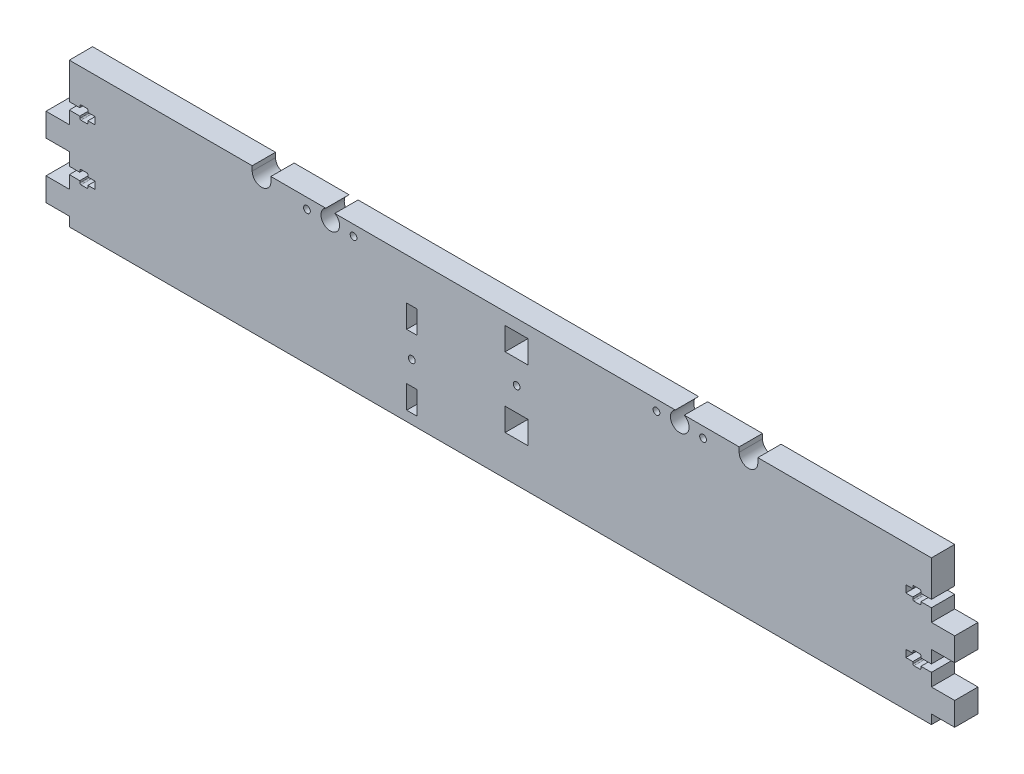
SolidWorks part; units mm, degrees
ref_plane "Front Plane" through (0, 0, 0) normal (0, 0, 1) x (1, 0, 0)
ref_plane "Top Plane" through (0, 0, 0) normal (0, 1, 0) x (1, 0, 0)
ref_plane "Right Plane" through (0, 0, 0) normal (1, 0, 0) x (0, 0, -1)
sketch "Sketch1" plane through (0, 0, 0) normal (0, 0, 1) x (1, 0, 0)
  line L0 (0, 0) -> (-185, 0)
  line L1 (-185, 0) -> (-185, -62) construction
  line L2 (0, -62) -> (-185, -62)
  line L3 (-185, -62) -> (-185, -58)
  line L4 (-185, -58) -> (-195, -58)
  line L5 (-195, -58) -> (-195, -48)
  line L6 (-195, -48) -> (-185, -48)
  line L7 (-185, -48) -> (-185, -34)
  line L8 (-185, -34) -> (-195, -34)
  line L9 (-195, -34) -> (-195, -24)
  line L10 (-195, -24) -> (-185, -24)
  line L11 (0, -62) -> (0, 0)
  line L12 (-185, -24) -> (-185, 0)
  line L13 (-195, -58) -> (-195, -24) construction
  line L14 (-195, -29) -> (-185, -29) construction
  line L15 (-195, -53) -> (-185, -53) construction
  dimension "D1" = 185
  dimension "D2" = 10
  dimension "D3" = 10
  dimension "D4" = 10
  dimension "D5" = 24
  dimension "D6" = 29
  dimension "D7" = 62
extrude "MainBody" add sketch "Sketch1" along normal blind 10
sketch "Sketch3" plane through (0, 0, 10) normal (0, 0, 1) x (1, 0, 0)
  line L0 (-185, -17) -> (-174, -17) construction
  line L1 (-185, 0) -> (-185, -24) construction
  line L2 (-185, -18.55) -> (-180.5, -18.55)
  line L3 (-180.5, -18.55) -> (-180.5, -19.35)
  line L4 (-180, -19.85) -> (-177.5, -19.85)
  line L5 (-177, -19.35) -> (-177, -18.55)
  line L6 (-177, -18.55) -> (-174, -18.55)
  line L7 (-174, -18.55) -> (-174, -15.45)
  line L8 (-180.5, -18.55) -> (-177, -18.55) construction
  line L9 (-195, -24) -> (-195, -34) construction
  line L10 (-180.5, -15.45) -> (-177, -15.45) construction
  line L11 (-177, -15.45) -> (-174, -15.45)
  line L12 (-177, -14.65) -> (-177, -15.45)
  line L13 (-180, -14.15) -> (-177.5, -14.15)
  line L14 (-180.5, -15.45) -> (-180.5, -14.65)
  line L15 (-185, -15.45) -> (-180.5, -15.45)
  line L16 (-185, -18.55) -> (-185, -15.45)
  line L17 (-185, -24) -> (-185, -34) construction
  line L19 (-195, -24) -> (-195, -34) construction
  line L20 (-195, -29) -> (-185, -29) construction
  line L21 (-180.5, -42.55) -> (-177, -42.55) construction
  line L22 (-180.5, -39.45) -> (-177, -39.45) construction
  line L23 (-185, -41) -> (-174, -41) construction
  line L24 (-185, -39.45) -> (-185, -42.55)
  line L25 (-185, -42.55) -> (-180.5, -42.55)
  line L26 (-180.5, -42.55) -> (-180.5, -43.35)
  line L27 (-180, -43.85) -> (-177.5, -43.85)
  line L28 (-177, -43.35) -> (-177, -42.55)
  line L29 (-177, -42.55) -> (-174, -42.55)
  line L30 (-174, -39.45) -> (-174, -42.55)
  line L31 (-177, -39.45) -> (-174, -39.45)
  line L32 (-177, -38.65) -> (-177, -39.45)
  line L33 (-180, -38.15) -> (-177.5, -38.15)
  line L34 (-180.5, -39.45) -> (-180.5, -38.65)
  line L35 (-185, -39.45) -> (-180.5, -39.45)
  line L36 (-180.5, -15.45) -> (-177, -15.45) construction
  arc A0 (-177.5, -19.85) -> (-177, -19.35) centre (-177.5, -19.35) ccw
  arc A1 (-180.5, -19.35) -> (-180, -19.85) centre (-180, -19.35) ccw
  arc A2 (-180.5, -14.65) -> (-180, -14.15) centre (-180, -14.65) cw
  arc A3 (-177.5, -14.15) -> (-177, -14.65) centre (-177.5, -14.65) cw
  arc A4 (-177.5, -43.85) -> (-177, -43.35) centre (-177.5, -43.35) ccw
  arc A5 (-180.5, -43.35) -> (-180, -43.85) centre (-180, -43.35) ccw
  arc A6 (-180.5, -38.65) -> (-180, -38.15) centre (-180, -38.65) cw
  arc A7 (-177.5, -38.15) -> (-177, -38.65) centre (-177.5, -38.65) cw
  point P6 (-195, -29)
  point P15 (-177, -19.85)
  point P18 (-180.5, -19.85)
  point P29 (-180.5, -14.15)
  point P30 (-177, -14.15)
  point P62 (-177, -43.85)
  point P63 (-180.5, -43.85)
  point P64 (-180.5, -38.15)
  point P65 (-177, -38.15)
  dimension "D2" = 8
  dimension "D7" = 0.5
  dimension "D1" = 11
  dimension "D3" = 1.55
  dimension "D4" = 2.85
  dimension "D5" = 12
  dimension "D6" = 3.5
extrude "ScrewCutouts" cut sketch "Sketch3" against normal through all
mirror "Mirror1" about plane through (0, 0, 0) normal (1, 0, 0) of "ScrewCutouts", "MainBody"
sketch "Sketch2" plane through (0, 0, 10) normal (0, 0, 1) x (1, 0, 0)
  line L0 (0, 0) -> (0, -62) construction
  line L1 (-185, -62) -> (185, -62) construction
  line L2 (2, 0) -> (2, -62) construction
  line L3 (185, 0) -> (-185, 0) construction
  line L4 (-63, -4.5) -> (-83, -4.5) construction
  line L5 (-73, -7.5) -> (-73, 0.5) construction
  line L6 (77, -7.5) -> (77, 0.5) construction
  line L7 (67, -4.5) -> (87, -4.5) construction
  circle A0 centre (-73, -3.5) radius 4
  circle A1 centre (-83, -4.5) radius 1.45
  circle A2 centre (-63, -4.5) radius 1.45
  circle A3 centre (67, -4.5) radius 1.45
  circle A4 centre (87, -4.5) radius 1.45
  circle A5 centre (77, -3.5) radius 4
  dimension "D1" = 2.9
  dimension "D2" = 8
  dimension "D4" = 3.5
  dimension "D5" = 75
  dimension "D6" = 2
  dimension "D3" = 10
  dimension "D7" = 1
extrude "RodCutouts" cut sketch "Sketch2" against normal through all
sketch "Sketch4" plane through (0, 0, 10) normal (0, 0, 1) x (1, 0, 0)
  line L0 (77, -3.5) -> (-73, -3.5) construction
  line L1 (2, -3.5) -> (2, -62) construction
  line L2 (-185, -62) -> (185, -62) construction
  line L3 (7, -44.9) -> (7, -5.1) construction
  line L4 (75.0635, 0) -> (-71.0635, 0) construction
  line L5 (7, -10) -> (7, -40) construction
  line L6 (2.05, -5.1) -> (11.95, -5.1)
  line L7 (2.05, -5.1) -> (2.05, -14.9)
  line L8 (2.05, -14.9) -> (11.95, -14.9)
  line L9 (11.95, -5.1) -> (11.95, -14.9)
  line L10 (2.05, -5.1) -> (11.95, -14.9) construction
  line L11 (2.05, -14.9) -> (11.95, -5.1) construction
  line L12 (2.05, -35.1) -> (11.95, -35.1)
  line L13 (2.05, -35.1) -> (2.05, -44.9)
  line L14 (2.05, -44.9) -> (11.95, -44.9)
  line L15 (11.95, -35.1) -> (11.95, -44.9)
  line L16 (2.05, -35.1) -> (11.95, -44.9) construction
  line L17 (2.05, -44.9) -> (11.95, -35.1) construction
  circle A0 centre (7, -25) radius 1.45
  point P12 (7, -10)
  point P17 (7, -40)
  dimension "D8" = 2.9
  dimension "D1" = 9.9
  dimension "D2" = 9.8
  dimension "D3" = 9.9
  dimension "D4" = 9.8
  dimension "D5" = 30
  dimension "D6" = 10
  dimension "D7" = 5
extrude "Cut-Extrude3" cut sketch "Sketch4" against normal through all
sketch "Sketch5" plane through (0, 0, 10) normal (0, 0, 1) x (1, 0, 0)
  line L0 (-38, 0) -> (-38, -62) construction
  line L1 (-74.9365, 0) -> (-185, 0) construction
  line L2 (-185, -62) -> (185, -62) construction
  line L3 (-40.2, -27.675) -> (-40.2, -47.825) construction
  line L4 (-40.2, -17.875) -> (-35.8, -17.875)
  line L5 (-40.2, -17.875) -> (-40.2, -27.675)
  line L6 (-40.2, -27.675) -> (-35.8, -27.675)
  line L7 (-35.8, -17.875) -> (-35.8, -27.675)
  line L8 (-40.2, -17.875) -> (-35.8, -27.675) construction
  line L9 (-40.2, -27.675) -> (-35.8, -17.875) construction
  line L10 (-40.2, -47.825) -> (-35.8, -47.825)
  line L11 (-40.2, -47.825) -> (-40.2, -57.725)
  line L12 (-40.2, -57.725) -> (-35.8, -57.725)
  line L13 (-35.8, -47.825) -> (-35.8, -57.725)
  line L14 (-40.2, -47.825) -> (-35.8, -57.725) construction
  line L15 (-40.2, -57.725) -> (-35.8, -47.825) construction
  line L16 (-35.8, -47.825) -> (-35.8, -27.675) construction
  line L17 (-40.2, -37.75) -> (-35.8, -37.75) construction
  line L18 (-73, -3.5) -> (77, -3.5) construction
  line L19 (2, -3.5) -> (2, -62) construction
  line L20 (2, -32.75) -> (-195, -32.75) construction
  line L21 (-195, -24) -> (-195, -34) construction
  line L22 (-31.6, 8.9944) -> (-31.6, 5) construction
  line L23 (75.0635, 0) -> (-71.0635, 0) construction
  line L24 (-28.4, 8.9944) -> (-28.4, 5)
  line L25 (-34.8, 8.9944) -> (-34.8, 5)
  circle A0 centre (-38, -37.75) radius 1.45
  arc A1 (-28.4, 8.9944) -> (-34.8, 8.9944) centre (-31.6, 8.9944) ccw
  arc A2 (-34.8, 5) -> (-28.4, 5) centre (-31.6, 5) ccw
  point P6 (-38, -22.775)
  point P11 (-38, -52.775)
  point P34 (-31.6, 6.9972)
  dimension "D3" = 9.9
  dimension "D4" = 9.8
  dimension "D5" = 30
  dimension "D6" = 2.9
  dimension "D9" = 3.2
  dimension "D1" = 4.4
  dimension "D2" = 0
  dimension "D7" = 40
  dimension "D8" = 5
  dimension "D10" = 5
  dimension "D11" = 1
extrude "EndstopHolder" cut sketch "Sketch5" against normal through all
sketch "Sketch6" plane through (0, 0, 10) normal (0, 0, 1) x (1, 0, 0)
  line L0 (-40.2, -47.825) -> (-40.2, -27.675) construction
  line L1 (-42.35, -47.825) -> (-27.8, -47.825) construction
  line L3 (-27.8, -53.825) -> (-27.8, -41.825) construction
  line L4 (-29.8, -53.825) -> (-29.8, -41.825)
  line L5 (-25.8, -53.825) -> (-25.8, -41.825)
  line L6 (-35.8, -47.825) -> (-40.2, -47.825) construction
  line L7 (-35.8, -57.725) -> (-35.8, -47.825) construction
  arc A0 (-29.8, -53.825) -> (-25.8, -53.825) centre (-27.8, -53.825) ccw
  arc A1 (-25.8, -41.825) -> (-29.8, -41.825) centre (-27.8, -41.825) ccw
  point P10 (-27.8, -47.825)
  dimension "D1" = 2
  dimension "D2" = 12
  dimension "D3" = 8
  dimension "D4" = 0
extrude "EndstopWires" [suppressed] cut sketch "Sketch6" against normal through all
sketch "Sketch7" plane through (0, 0, 10) normal (0, 0, 1) x (1, 0, 0)
  line L0 (-73, -3.5) -> (77, -3.5) construction
  line L1 (2, -3.5) -> (2, -62) construction
  line L3 (-102.5, 0) -> (-102.5, -2) construction
  line L4 (-74.9365, 0) -> (-185, 0) construction
  line L5 (-98.5, 0) -> (-98.5, -2)
  line L6 (-106.5, 0) -> (-106.5, -2)
  line L7 (106.5, 0) -> (106.5, -2) construction
  line L8 (102.5, 0) -> (102.5, -2)
  line L9 (110.5, 0) -> (110.5, -2)
  line L10 (-185, -62) -> (185, -62) construction
  arc A0 (-98.5, 0) -> (-106.5, 0) centre (-102.5, 0) ccw
  arc A1 (-106.5, -2) -> (-98.5, -2) centre (-102.5, -2) ccw
  arc A2 (102.5, 0) -> (110.5, 0) centre (106.5, 0) cw
  arc A3 (110.5, -2) -> (102.5, -2) centre (106.5, -2) cw
  point P12 (-102.5, -1)
  point P19 (106.5, -1)
  dimension "D3" = 4
  dimension "D1" = 2
  dimension "D2" = 104.5
extrude "Cut-Extrude4" cut sketch "Sketch7" against normal through all
equation "\"Y-ROD-SPACING\"=75"
equation "\"D5@Sketch2\"=\"Y-ROD-SPACING\""
equation "\"Y-BED-OFFSET\"=2"
equation "\"D6@Sketch2\"=\"Y-BED-OFFSET\""
equation "\"T-SLOT-NUT-FILLET-RADIUS\"=0.5"
equation "\"D7@Sketch3\"=\"T-SLOT-NUT-FILLET-RADIUS\""
equation "\"T-SLOT-SCREW-SHAFT-RADIUS\"=1.55"
equation "\"D3@Sketch3\"=\"T-SLOT-SCREW-SHAFT-RADIUS\""
equation "\"T-SLOT-SCREW-SHAFT-CUTOUT-LENGTH\"=11.0"
equation "\"D1@Sketch3\"=\"T-SLOT-SCREW-SHAFT-CUTOUT-LENGTH\""
equation "\"T-SLOT-NUT-DEPTH\"=3.5"
equation "\"D6@Sketch3\"=\"T-SLOT-NUT-DEPTH\""
equation "\"T-SLOT-NUT-WIDTH\"=2.85"
equation "\"D4@Sketch3\"=\"T-SLOT-NUT-WIDTH\""
equation "\"T-SLOT-NUT-END-DISTANCE\"=8"
equation "\"D2@Sketch3\"=\"T-SLOT-NUT-END-DISTANCE\""
equation "\"ACRYLIC-TAB-CUTOUT-SIZE\"=\"ACRYLIC-THICKNESS\"+\"ACRYLIC-TAB-TOLERANCE\"*2"
equation "\"D1@Sketch4\"=\"ACRYLIC-THICKNESS\"-\"KERF\"*2"
equation "\"D2@Sketch4\"=\"ACRYLIC-TAB-WIDTH\"-\"KERF\"*4"
equation "\"D3@Sketch4\"=\"ACRYLIC-THICKNESS\"-\"KERF\"*2"
equation "\"D4@Sketch4\"=\"ACRYLIC-TAB-WIDTH\"-\"KERF\"*4"
equation "\"ACRYLIC-M3-HOLE\"=2.9"
equation "\"D8@Sketch4\"=\"ACRYLIC-M3-HOLE\""
equation "\"Y-BED-ROD-INSET\"=3.5"
equation "\"D1@Sketch2\"=\"ACRYLIC-M3-HOLE\""
equation "\"D4@Sketch2\"=\"Y-BED-ROD-INSET\""
equation "\"SMOOTHROD-CAP-SCREW-DISTANCE\"=20"
equation "\"D3@Sketch2\"=\"SMOOTHROD-CAP-SCREW-DISTANCE\"/2"
equation "\"ACRYLIC-TAB-WIDTH\"=\"ACRYLIC-THICKNESS\""
equation "\"FRAME-WIDTH-INNER\"=370"
equation "\"D2@Sketch1\"=\"ACRYLIC-TAB-WIDTH\""
equation "\"D3@Sketch1\"=\"ACRYLIC-TAB-WIDTH\""
equation "\"D4@Sketch1\"=\"ACRYLIC-TAB-WIDTH\""
equation "\"D1@Sketch1\"=\"FRAME-WIDTH-INNER\"/2"
equation "\"X-ROD-SPACING\"=45"
equation "\"Z-ROD-SPACING\"=17.5"
equation "\"ACRYLIC-THICKNESS\"=10"
equation "\"ACRYLIC-THICKNESS2\"=4.5"
equation "\"NEMA17-HOLE-SPACING\"=31"
equation "\"NEMA17-CENTRAL-CUTOUT\"=22.5"
equation "\"Z-BRACKET-REACH\"=55"
equation "\"TOP-BRACKET-SPACING\"=40"
equation "\"SMOOTHROD-X-LENGTH\"=350"
equation "\"SMOOTHROD-Y-LENGTH\"=350"
equation "\"SMOOTHROD-Z-LENGTH\"=350"
equation "\"SMOOTHROD-TIGHTENING-HEADROOM\"=.25"
equation "\"LEADSCREW-Z-LENGTH\"=300"
equation "\"SCREW-LENGTH-FRAME\"=\"ACRYLIC-THICKNESS\" + 10"
equation "\"SCREW-HEAD-RADIUS\"=6"
equation "\"PRINTED-X-SMOOTHROD-DIAMETER\"=8.4"
equation "\"PRINTED-X-SMOOTHROD-CUTOUT\"=10"
equation "\"PRINTED-X-BASE-HEIGHT\"=10"
equation "\"PRINTED-LM8UU-CUTOUT-SIZE\"=15.5"
equation "\"PRINTED-LM8UU-CUTOUT-LENGTH\"=24.5"
equation "\"PRINTED-X-IDLER-HEIGHT\"=16"
equation "\"PSU-MOUNTING-WIDTH\"=95"
equation "\"PSU-MOUNTING-HEIGHT\"=177"
equation "\"D1@MainBody\"=\"ACRYLIC-THICKNESS\""
equation "\"D1@Sketch5\"=\"ACRYLIC-THICKNESS2\"-\"KERF\"*2"
equation "\"D3@Sketch5\"=\"ACRYLIC-TAB-CUTOUT-SIZE\""
equation "\"D4@Sketch5\"=\"ACRYLIC-TAB-WIDTH\"-\"KERF\"*4"
equation "\"D6@Sketch5\"=\"ACRYLIC-M3-HOLE\""
equation "\"Y-BED-SCREW-SPACING\"=209"
equation "\"Y-BED-SCREW-CUTOUT-SLOT-HEIGHT\"=2"
equation "\"Z-ROD-INSET\"=16"
equation "\"Y-BELT-TO-ROD-DISTANCE\"=20"
equation "\"SPOOL-HOLDER-ROD-SPACING\"=150"
equation "\"D1@Sketch7\"=\"Y-BED-SCREW-CUTOUT-SLOT-HEIGHT\""
equation "\"D2@Sketch7\"=\"Y-BED-SCREW-SPACING\"/2"
equation "\"ACRYLIC-TAB-TOLERANCE\"=-.05"
equation "\"SCREW-LENGTH-MOTOR\"=\"ACRYLIC-THICKNESS\" + 5"
equation "\"SCREW-LENGTH-EXTRUDER\"=28"
equation "\"ACRYLIC-X-CARRIAGE-WIDTH\"=55"
equation "\"ACRYLIC-X-CARRIAGE-HEIGHT\"=75"
equation "\"ACRYLIC-X-CARRIAGE-LM8UU-CUTOUT-WIDTH\"=24.25"
equation "\"ACRYLIC-X-CARRIAGE-SCREW-SPACING-X\"=15"
equation "\"ACRYLIC-X-CARRIAGE-SCREW-SPACING-Y\"=33"
equation "\"ACRYLIC-X-CARRIAGE-CENTER-TAB-SPACING\"=14"
equation "\"ACRYLIC-X-CARRIAGE-EXTRUDER-OFFSET\"=26"
equation "\"ACRYLIC-X-CARRIAGE-EXTRUDER-ANGLE\"=90"
equation "\"ACRYLIC-X-CARRIAGE-EXTRUDER-SHELF-DEPTH\"=\"ACRYLIC-X-CARRIAGE-EXTRUDER-OFFSET\" + 28"
equation "\"ACRYLIC-X-CARRIAGE-EXTRUDER-BRACE-SPACING\"=23"
equation "\"ACRYLIC-X-CARRIAGE-EXTRUDER-BRACE-TAB-OFFSET\"=20"
equation "\"ACRYLIC-X-CARRIAGE-EXTRUDER-BRACE-HEIGHT\"=35"
equation "\"ACRYLIC-X-CARRIAGE-EXTRUDER-BRACE-SCREW-SPACING\"=22"
equation "\"PRINTED-M3-HOLE\"=3.5"
equation "\"ACRYLIC-X-CARRIAGE-LM8UU-CUTOUT-HEIGHT\"=11.0"
equation "\"ACRYLIC-X-CARRIAGE-DUAL-WIDTH-MULTIPLIER\"=1.65"
equation "\"ACRYLIC-X-CARRIAGE-DUAL-HOTEND-SPACING\"=42"
equation "\"ACRYLIC-X-CARRIAGE-DUAL-WIDTH\"=75"
equation "\"ACRYLIC-X-CARRIAGE-DUAL-HOTEND-SEPARATION\"=36"
equation "\"ACRYLIC-X-CARRIAGE-DUAL-MOUNT-PLATE-DEPTH\"=75"
equation "\"ACRYLIC-X-CARRIAGE-DUAL-MOUNT-BRACE-WIDTH\"=33"
equation "\"ACRYLIC-X-CARRIAGE-DUAL-MOUNT-SCREW-WIDTH\"=40"
equation "\"BLOWER-FAN-WIDTH\"=15"
equation "\"KERF\"=0.05"
equation "\"PRINTED-M3-NUT-AF\"=6.25"
equation "\"ACRYLIC-X-CARRIAGE-DUAL-FAN-OFFSET\"=52"
equation "\"ACRYLIC-X-CARRIAGE-DUAL-FAN-HEIGHT\"=20"
